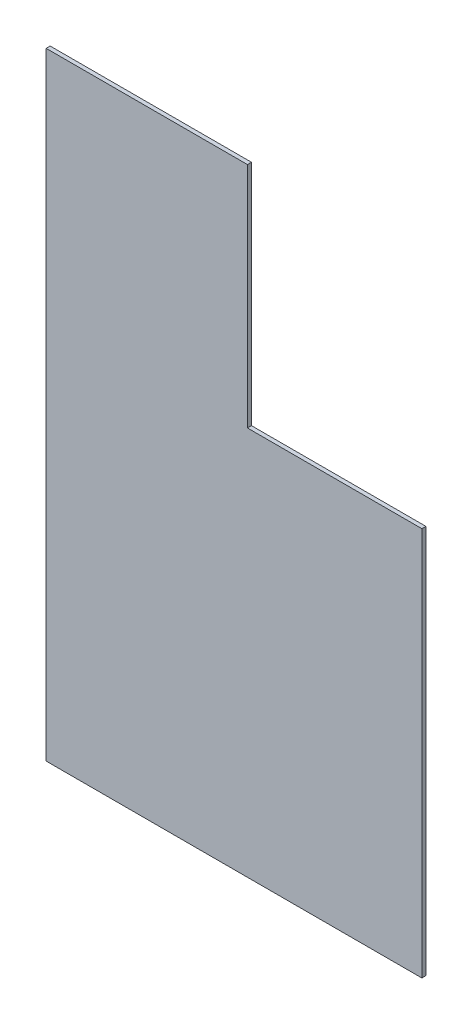
SolidWorks part; units mm, degrees
ref_plane "Plan de face" through (0, 0, 0) normal (0, 0, 1) x (1, 0, 0)
ref_plane "Plan de dessus" through (0, 0, 0) normal (0, 1, 0) x (1, 0, 0)
ref_plane "Plan de droite" through (0, 0, 0) normal (1, 0, 0) x (0, 0, -1)
sketch "Esquisse1" plane through (0, 0, 0) normal (0, 0, 1) x (1, 0, 0)
  line L0 (-158.4145, -408.6715) -> (121.5855, -408.6715)
  line L1 (-158.4145, 51.3285) -> (-8.4145, 51.3285)
  line L2 (-158.4145, 51.3285) -> (-158.4145, -408.6715)
  line L5 (-8.4145, -118.6715) -> (121.5855, -118.6715)
  line L6 (-8.4145, 51.3285) -> (-8.4145, -118.6715)
  line L10 (121.5855, -118.6715) -> (121.5855, -408.6715)
  dimension "D2" = 150
  dimension "D1" = 460
  dimension "D3" = 170
  dimension "D4" = 280
extrude "Boss.-Extru.1" add sketch "Esquisse1" along normal blind 3
equation "\"ProfondeurBoite\"=460"
equation "\"D1@Esquisse1\"=\"ProfondeurBoite\""
equation "\"LongueurSyphon\"=170"
equation "\"D3@Esquisse1\"= \"LongueurSyphon\""
equation "\"LargeurSyphon\"=120"
equation "\"D4@Esquisse1\"= \"LargeurBoite\""
equation "\"EpaisseurPlaque\"= 3"
equation "\"HauteurSyphon\"=\"HauteurCoteGauche\"-\"HauteurSolSyphon\""
equation "\"D1@Boss.-Extru.1\"=\"EpaisseurPlaque\""
equation "\"HauteurCoteDroit\"= 490"
equation "\"HauteurCoteGauche\"= 540"
equation "\"HauteurSolSyphon\"= 300"
equation "\"LargeurDroite\"=10"
equation "\"LargeurGauche\"=150"
equation "\"LargeurBoite\"= \"LargeurDroite\" + \"LargeurGauche\" + \"LargeurSyphon\""
equation "\"D2@Esquisse1\"=\"LargeurGauche\""
